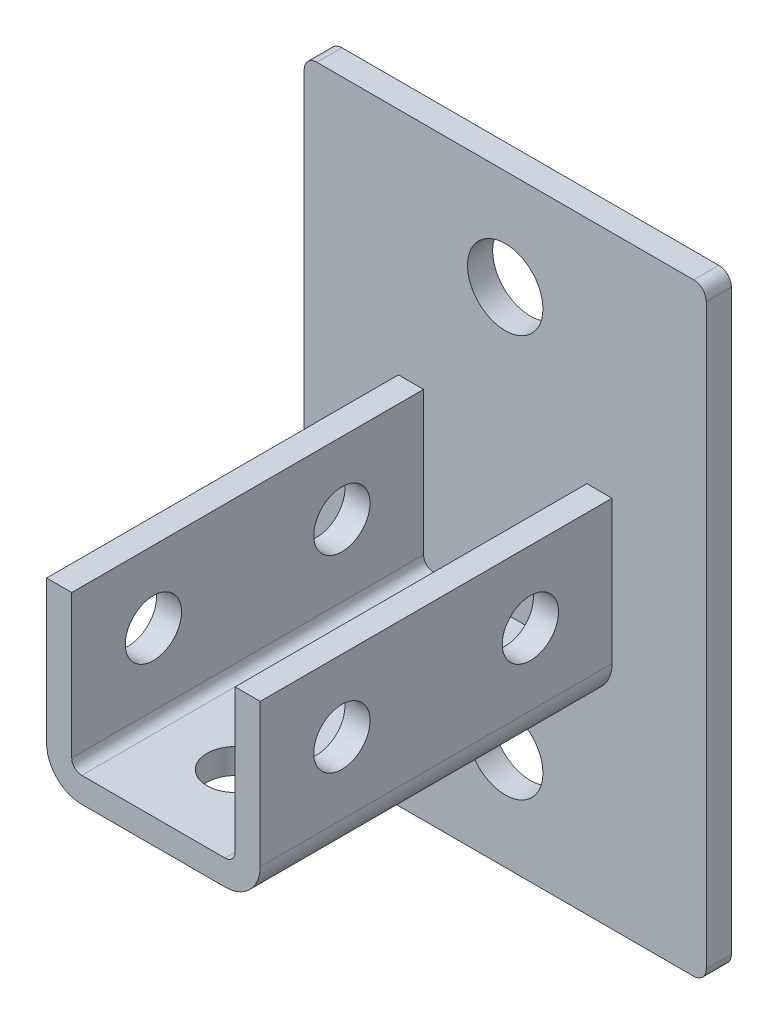
SolidWorks part; units mm, degrees
note: '?' marks a value the reader was unsure of.
ref_plane "Front Plane" through (0, 0, 0) normal (0, 0, 1) x (1, 0, 0)
ref_plane "Top Plane" through (0, 0, 0) normal (0, 1, 0) x (1, 0, 0)
ref_plane "Right Plane" through (0, 0, 0) normal (1, 0, 0) x (0, 0, -1)
sketch "Sketch1" plane through (0, 0, 0) normal (0, 0, 1) x (1, 0, 0)
  line L0 (-50.8, -76.2) -> (50.8, 76.2) construction
  line L1 (-47.625, 76.2) -> (47.625, 76.2)
  line L2 (-50.8, 73.025) -> (-50.8, -73.025)
  line L3 (-47.625, -76.2) -> (47.625, -76.2)
  line L4 (50.8, 73.025) -> (50.8, -73.025)
  circle A0 centre (0, 50.8) radius 9.525
  circle A1 centre (0, -50.8) radius 9.525
  arc A2 (50.8, 73.025) -> (47.625, 76.2) centre (47.625, 73.025) ccw
  arc A3 (-50.8, -73.025) -> (-47.625, -76.2) centre (-47.625, -73.025) ccw
  arc A4 (47.625, -76.2) -> (50.8, -73.025) centre (47.625, -73.025) ccw
  arc A5 (-47.625, 76.2) -> (-50.8, 73.025) centre (-47.625, 73.025) ccw
  point P19 (-50.8, 76.2)
  dimension "D3" = 19.05
  dimension "D6" = 3.175
  dimension "D1" = 101.6
  dimension "D2" = 152.4
  dimension "D4" = 25.4
  dimension "D5" = 25.4
extrude "Boss-Extrude1" add sketch "Sketch1" along normal blind 6.35
sketch "Sketch2" plane through (0, 0, 6.35) normal (0, 0, 1) x (1, 0, 0)
  line L0 (-20.6375, -20.6375) -> (20.6375, 20.6375) construction
  line L1 (-18.0975, 20.6375) -> (18.0975, 20.6375) construction
  line L2 (-20.6375, 18.0975) -> (-20.6375, -18.0975)
  line L3 (-18.0975, -20.6375) -> (18.0975, -20.6375)
  line L4 (20.6375, 18.0975) -> (20.6375, -18.0975)
  arc A0 (18.0975, -20.6375) -> (20.6375, -18.0975) centre (18.0975, -18.0975) ccw
  arc A1 (-20.6375, -18.0975) -> (-18.0975, -20.6375) centre (-18.0975, -18.0975) ccw
  arc A2 (18.0975, 20.6375) -> (20.6375, 18.0975) centre (18.0975, 18.0975) cw construction
  arc A3 (-18.0975, 20.6375) -> (-20.6375, 18.0975) centre (-18.0975, 18.0975) ccw construction
  point P15 (-20.6375, 20.6375)
  dimension "D2" = 2.54
  dimension "D3" = 2.54
  dimension "D1" = 41.275
extrude "Extrude-Thin1" add sketch "Sketch2" along normal blind 88.9 thin
sketch "Sketch3" plane through (0, 0, 0) normal (0, -1, 0) x (1, 0, 0)
  line L0 (18.0975, 95.25) -> (-18.0975, 95.25) construction
  line L3 (0, 74.6125) -> (0, 26.9875) construction
  circle A0 centre (0, 74.6125) radius 7.112
  circle A1 centre (0, 26.9875) radius 7.112
  dimension "D3" = 14.224
  dimension "D1" = 47.625
  dimension "D2" = 20.6375
extrude "Cut-Extrude1" cut sketch "Sketch3" along normal through all
ref_axis "Axis1" through (0, 0, 74.6125) along (0, 0, -1)
pattern_circular "CirPattern1" count 4 over 360 about axis through (0, 0, 74.6125) along (0, 0, -1) skipping 2 of "Cut-Extrude1"
ref_plane "Contact Plane 1" through (0, 0, 6.35) normal (0, 0, 1) x (1, 0, 0)
ref_plane "Contact Plane 2" through (0, -20.6375, 0) normal (0, 1, 0) x (1, 0, 0)
ref_axis "Center Axis 1" through (0, -50.8, 6.35) along (0, 0, -1)?
ref_axis "Center Axis 2" through (20.6375, 0, 26.9875) along (1, 0, 0)?
